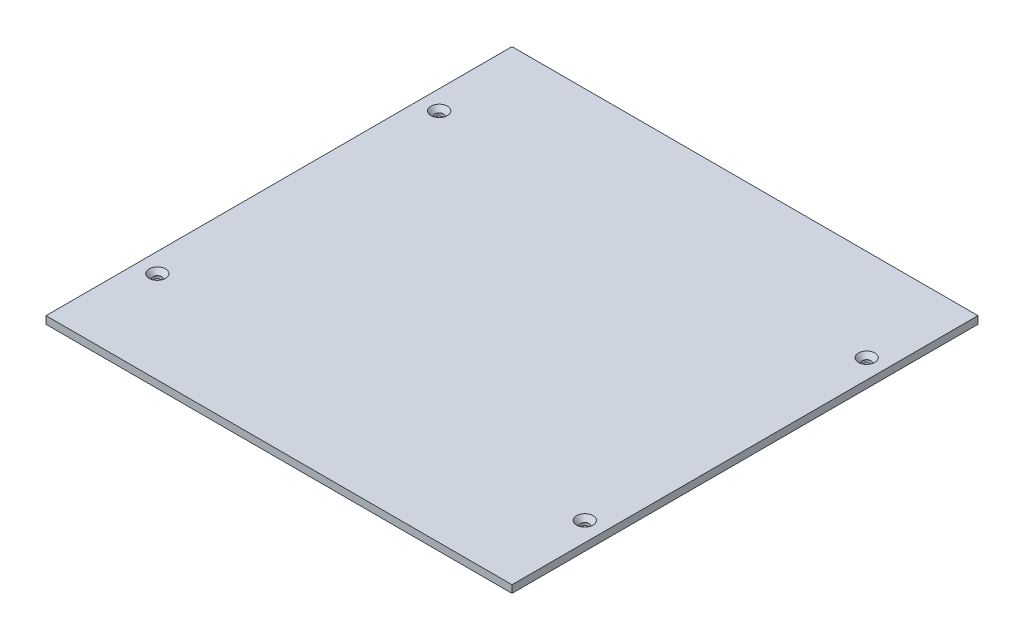
SolidWorks part; units mm, degrees
material "6061-T4 (SS)"
ref_plane "Front Plane" through (0, 0, 0) normal (0, 0, 1) x (1, 0, 0)
ref_plane "Top Plane" through (0, 0, 0) normal (0, 1, 0) x (1, 0, 0)
ref_plane "Right Plane" through (0, 0, 0) normal (1, 0, 0) x (0, 0, -1)
sketch "Sketch1" plane through (0, 0, 0) normal (0, 1, 0) x (1, 0, 0)
  line L1 (0, 0) -> (99.2004, 0)
  line L2 (0, 0) -> (0, 99.2004)
  line L3 (0, 99.2004) -> (99.2004, 99.2004)
  line L4 (99.2004, 0) -> (99.2004, 99.2004)
  dimension "D1" = 99.2004
  dimension "D2" = 99.2004
extrude "Boss-Extrude1" add sketch "Sketch1" along normal blind 1.6002
sketch "Sketch3" plane through (0, 1.6002, 0) normal (0, 1, 0) x (1, 0, 0)
  line L0 (0, 0) -> (1.6002, 0) construction
  line L1 (0, 0) -> (99.2004, 0) construction
  line L2 (1.6002, 0) -> (1.6002, 99.2004) construction
  line L3 (99.2004, 99.2004) -> (0, 99.2004) construction
  line L4 (0, 97.6002) -> (1.6002, 97.6002) construction
  line L5 (0, 99.2004) -> (0, 0) construction
  line L6 (1.6002, 97.6002) -> (97.6002, 97.6002) construction
  line L7 (97.6002, 97.6002) -> (97.6002, 99.2004) construction
  line L8 (97.6002, 97.6002) -> (97.6002, 0) construction
  line L9 (99.2004, 0) -> (99.2004, 99.2004) construction
  line L10 (49.6002, 97.6002) -> (49.6002, 49.6002) construction
  line L11 (95.1002, 49.6002) -> (4.1002, 49.6002) construction
  line L12 (4.1002, 49.6002) -> (4.1002, 79.6002) construction
  line L13 (4.1002, 49.6002) -> (4.1002, 19.6002) construction
  line L14 (95.1002, 49.6002) -> (95.1002, 19.6002) construction
  line L15 (95.1002, 49.6002) -> (95.1002, 79.6002) construction
  line L16 (1.6002, 1.6002) -> (97.6002, 1.6002) construction
  line L17 (49.6002, 49.6002) -> (49.6002, 1.6002) construction
  dimension "D1" = 1.6002
  dimension "D2" = 1.6002
  dimension "D3" = 1.6002
  dimension "D4" = 2.5
  dimension "D5" = 30
  dimension "D6" = 1.6002
hole_wizard "CSK for #0 Flat Head Socket Cap Screw1" positions "Sketch4" profile "Sketch5" countersink size "#0" standard "ANSI Inch" end condition through all
sketch "Sketch4" plane through (0, 1.6002, 0) normal (0, 1, 0) x (1, 0, 0)
  point P0 (4.1002, 79.6002)
  point P3 (4.1002, 19.6002)
  point P6 (95.1002, 19.6002)
  point P9 (95.1002, 79.6002)
sketch "Sketch5" plane through (4.1002, 1.6002, -79.6002) normal (1, 0, 0) x (0, 0, 1)
  line L0 (0, 0) -> (0, 1.6002)
  line L1 (0, 1.6002) -> (0.889, 1.6002)
  line L2 (0.889, 1.6002) -> (0.889, 0.9935)
  line L3 (0.889, 0.9935) -> (1.7526, 0)
  line L5 (1.7526, 0) -> (0, 0)
  line L6 (-0.889, 0.9935) -> (-1.7526, 0) construction
  line L11 (0, -6.35) -> (0, 107.95) construction
  dimension "Thru Hole Dia." = 1.778
  dimension "Thru Hole Depth" = 1.6002
  dimension "Near C'Sink Dia." = 3.5052
  dimension "Near C'Sink Angle" = 82
